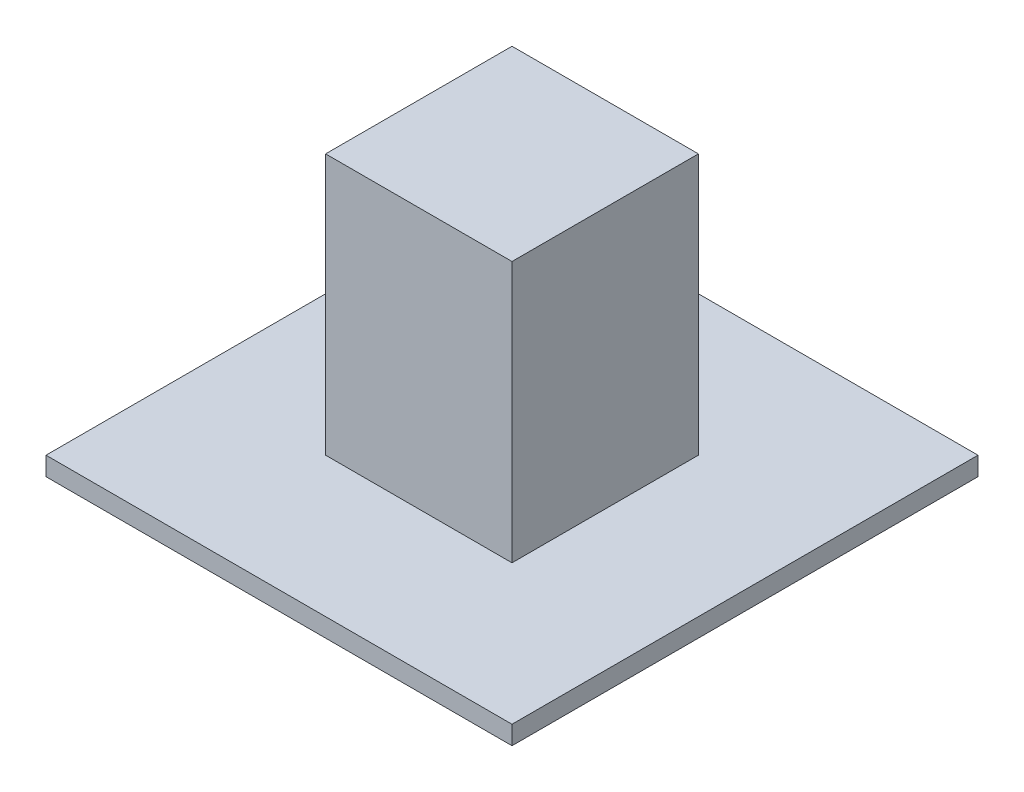
SolidWorks part; units mm, degrees
ref_plane "Front Plane" through (0, 0, 0) normal (0, 0, 1) x (1, 0, 0)
ref_plane "Top Plane" through (0, 0, 0) normal (0, 1, 0) x (1, 0, 0)
ref_plane "Right Plane" through (0, 0, 0) normal (1, 0, 0) x (0, 0, -1)
sketch "Sketch1" plane through (0, 0, 0) normal (0, 1, 0) x (1, 0, 0)
  line L1 (-1, -1) -> (1, -1)
  line L2 (-1, -1) -> (-1, 1)
  line L3 (-1, 1) -> (1, 1)
  line L4 (1, -1) -> (1, 1)
  line L5 (-1, -1) -> (1, 1) construction
  line L6 (-1, 1) -> (1, -1) construction
  point P0 (0, 0)
  dimension "D1" = 2
  dimension "D2" = 2
extrude "Boss-Extrude1" add sketch "Sketch1" along normal blind 2.8
sketch "Sketch2" plane through (0, 0, 0) normal (0, 1, 0) x (1, 0, 0)
  line L1 (-2.5, -2.5) -> (2.5, -2.5)
  line L2 (-2.5, -2.5) -> (-2.5, 2.5)
  line L3 (-2.5, 2.5) -> (2.5, 2.5)
  line L4 (2.5, -2.5) -> (2.5, 2.5)
  line L5 (-2.5, -2.5) -> (2.5, 2.5) construction
  line L6 (-2.5, 2.5) -> (2.5, -2.5) construction
  point P0 (0, 0)
  dimension "D1" = 5
  dimension "D2" = 5
extrude "Boss-Extrude2" add sketch "Sketch2" against normal blind 0.2
sketch "Sketch3" plane through (0, -0.2, 0) normal (0, -1, 0) x (-1, 0, 0)
  line L0 (-2.5, 0) -> (2.5, 0) construction
  line L1 (-2.5, -2.5) -> (-2.5, 2.5) construction
  line L2 (2.5, 2.5) -> (2.5, -2.5) construction
  line L3 (0, 2.5) -> (0, -2.5) construction
  line L4 (-2.5, 2.5) -> (2.5, 2.5) construction
  line L5 (2.5, -2.5) -> (-2.5, -2.5) construction
  circle A0 centre (0, 0) radius 0.5
  point P14 (0, 0)
  dimension "D1" = 1
extrude "Boss-Extrude3" add sketch "Sketch3" along normal blind 1
